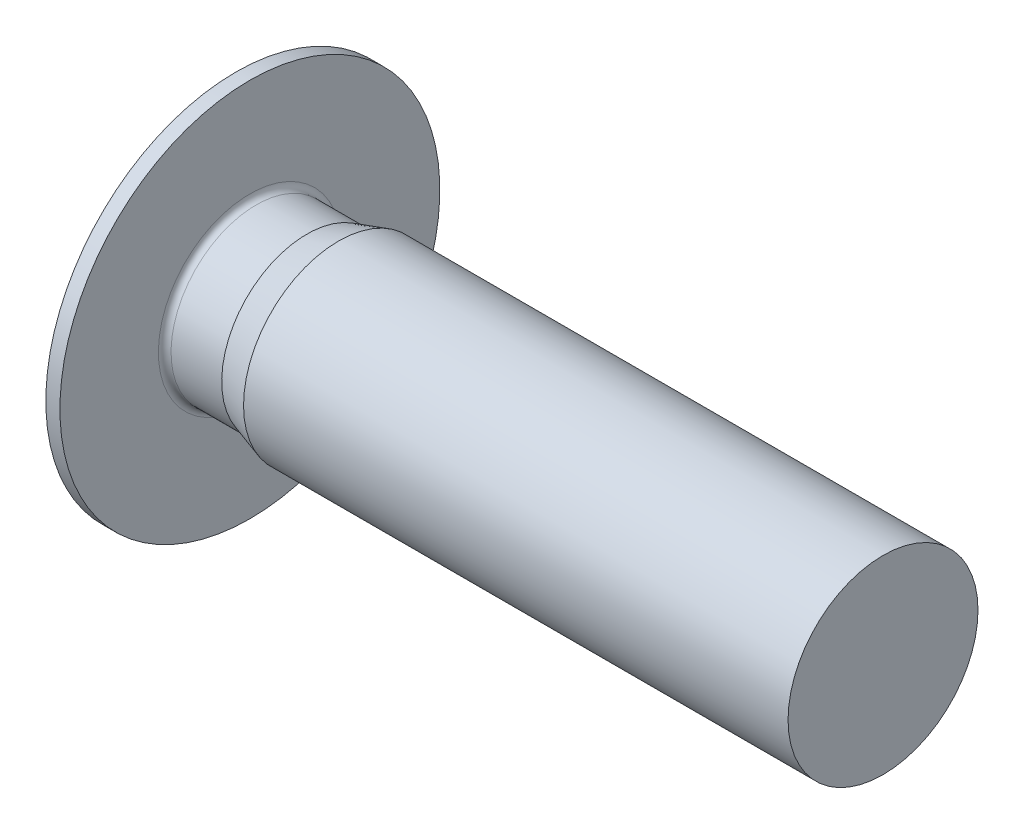
SolidWorks part; units mm, degrees
material "SCM435"
ref_plane "Front Plane" through (0, 0, 0) normal (0, 0, 1) x (1, 0, 0)
ref_plane "Top Plane" through (0, 0, 0) normal (0, 1, 0) x (1, 0, 0)
ref_plane "Right Plane" through (0, 0, 0) normal (1, 0, 0) x (0, 0, -1)
sketch "Sketch1" plane through (0, 0, 0) normal (0, 0, 1) x (1, 0, 0)
  line L0 (-0.8, 0) -> (10, 0) construction
  line L1 (-0.8, 0) -> (-0.8, 2)
  line L2 (-0.2226, 3) -> (0, 3)
  line L3 (0, 3) -> (0, 1.345)
  line L4 (1.4, 1.5) -> (10, 1.5)
  line L5 (10, 1.5) -> (10, 0)
  line L6 (10, 0) -> (-0.8, 0)
  line L7 (1.4, 1.5) -> (0.9, 1.345)
  line L8 (0.9, 1.345) -> (0, 1.345)
  line L9 (-0.2226, 3) -> (-0.8, 2)
  line L10 (-0.8, 0) -> (10, 0) construction
  dimension "A" = 6
  dimension "M" = 3
  dimension "L" = 10
  dimension "MSM_1" = 4
  dimension "E_s" = 1.4
  dimension "E" = 0.8
  dimension "FIX_1" = 30
  dimension "MSM_2" = 2.69
  dimension "MSM_3" = 0.5
revolve "Revolve1" add sketch "Sketch1" angle 360 about L0
cosmetic thread "Thread1" parameters "ATL_1"=8.6, "ATD"=2.459
fillet "Fillet1" radius 0.1 1 edges at (0, -1.345, 0)
sketch "Sketch2" plane through (-0.8, 0, 0) normal (-1, 0, 0) x (0, 0, 1)
  line L1 (0, 0.866) -> (-0.75, 0.433)
  line L2 (-0.75, 0.433) -> (-0.75, -0.433)
  line L3 (-0.75, -0.433) -> (0, -0.866)
  line L4 (0, -0.866) -> (0.75, -0.433)
  line L5 (0.75, -0.433) -> (0.75, 0.433)
  line L6 (0.75, 0.433) -> (0, 0.866)
  circle A0 centre (0, 0) radius 0.75 construction
  dimension "B" = 1.5
extrude "Cut-Extrude1" cut sketch "Sketch2" against normal blind 2
sketch "Sketch3" plane through (0, 0, 0) normal (0, 0, 1) x (1, 0, 0)
  line L0 (1.2, 0) -> (1.6506, 0) construction
  line L1 (1.2, 0) -> (1.2, 0.75)
  line L2 (1.2, 0.75) -> (1.6506, 0)
  line L3 (1.6506, 0) -> (1.2, 0)
  line L5 (1.2, 0.433) -> (1.2, -0.433) construction
  dimension "FIX_3" = 59
  dimension "B" = 1.5
revolve "Cut-Revolve1" cut sketch "Sketch3" angle 360 about L0
equation "\"ATL_1@Thread1\" = \"L@Sketch1\" - \"E_s@Sketch1\""
